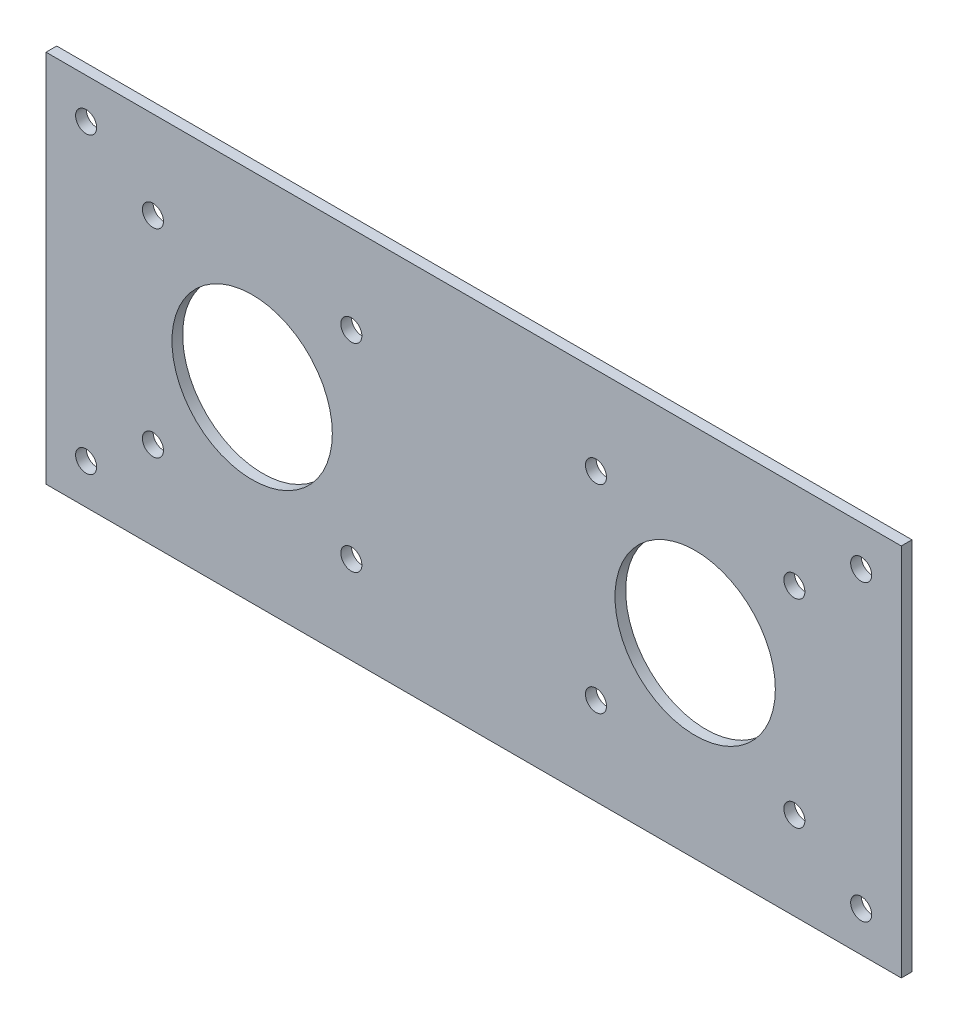
SolidWorks part; units mm, degrees
ref_plane "Front Plane" through (0, 0, 0) normal (0, 0, 1) x (1, 0, 0)
ref_plane "Top Plane" through (0, 0, 0) normal (0, 1, 0) x (1, 0, 0)
ref_plane "Right Plane" through (0, 0, 0) normal (1, 0, 0) x (0, 0, -1)
sketch "Sketch2" plane through (0, 0, 0) normal (0, 0, 1) x (1, 0, 0)
  line L0 (-29.06, 23.57) -> (-76.2, 23.57) construction
  line L1 (-101.6, -44.45) -> (101.6, -44.45)
  line L2 (-101.6, -44.45) -> (-101.6, 44.45)
  line L3 (-101.6, 44.45) -> (101.6, 44.45)
  line L4 (101.6, -44.45) -> (101.6, 44.45)
  line L5 (-101.6, -44.45) -> (101.6, 44.45) construction
  line L6 (-101.6, 44.45) -> (101.6, -44.45) construction
  line L7 (-76.2, 23.57) -> (-76.2, -23.57) construction
  line L8 (-76.2, -23.57) -> (-29.06, -23.57) construction
  line L9 (-29.06, -23.57) -> (-29.06, 23.57) construction
  line L10 (-76.2, 0) -> (-101.6, 0) construction
  line L11 (-52.63, 0) -> (-52.63, 23.57) construction
  line L12 (29.06, -23.57) -> (76.2, -23.57) construction
  line L13 (76.2, -23.57) -> (76.2, 23.57) construction
  line L14 (76.2, 23.57) -> (29.06, 23.57) construction
  line L15 (29.06, 23.57) -> (29.06, -23.57) construction
  line L16 (-52.63, 0) -> (-29.06, 0) construction
  line L17 (76.2, 0) -> (101.6, 0) construction
  line L18 (52.63, 0) -> (29.06, 0) construction
  line L19 (52.63, 0) -> (52.63, 23.57) construction
  circle A0 centre (-76.2, -23.57) radius 2.5
  circle A1 centre (-29.06, -23.57) radius 2.5
  circle A2 centre (-29.06, 23.57) radius 2.5
  circle A3 centre (-76.2, 23.57) radius 2.5
  circle A4 centre (29.06, 23.57) radius 2.5
  circle A5 centre (76.2, 23.57) radius 2.5
  circle A7 centre (29.06, -23.57) radius 2.5
  circle A8 centre (76.2, -23.57) radius 2.5
  circle A9 centre (-52.63, 0) radius 19.05
  circle A10 centre (52.63, 0) radius 19.05
  point P0 (0, 0)
  point P17 (101.6, 0)
  point P23 (-101.6, 0)
  dimension "D3" = 5
  dimension "D6" = 38.1
  dimension "D1" = 47.14
  dimension "D2" = 88.9
  dimension "D4" = 203.2
  dimension "D5" = 25.4
extrude "Boss-Extrude1" add sketch "Sketch2" along normal mid plane 2.54
sketch "Sketch3" plane through (0, 0, 1.27) normal (0, 0, 1) x (1, 0, 0)
  line L0 (-101.6, 34.925) -> (-92.075, 34.925) construction
  line L1 (-101.6, 44.45) -> (-101.6, -44.45) construction
  line L2 (-92.075, 34.925) -> (-92.075, 44.45) construction
  line L3 (101.6, 44.45) -> (-101.6, 44.45) construction
  line L4 (92.075, 44.45) -> (92.075, 34.925) construction
  line L5 (92.075, 34.925) -> (101.6, 34.925) construction
  line L6 (101.6, -44.45) -> (101.6, 44.45) construction
  line L7 (92.075, -44.45) -> (92.075, -34.925) construction
  line L8 (-101.6, -44.45) -> (101.6, -44.45) construction
  line L9 (92.075, -34.925) -> (101.6, -34.925) construction
  line L10 (-92.075, -44.45) -> (-92.075, -34.925) construction
  line L11 (-92.075, -34.925) -> (-101.6, -34.925) construction
  circle A0 centre (-92.075, 34.925) radius 2.5
  circle A1 centre (-92.075, -34.925) radius 2.5
  circle A2 centre (92.075, -34.925) radius 2.5
  circle A3 centre (92.075, 34.925) radius 2.5
  dimension "D2" = 5
  dimension "D1" = 9.525
extrude "Cut-Extrude1" cut sketch "Sketch3" against normal through all
